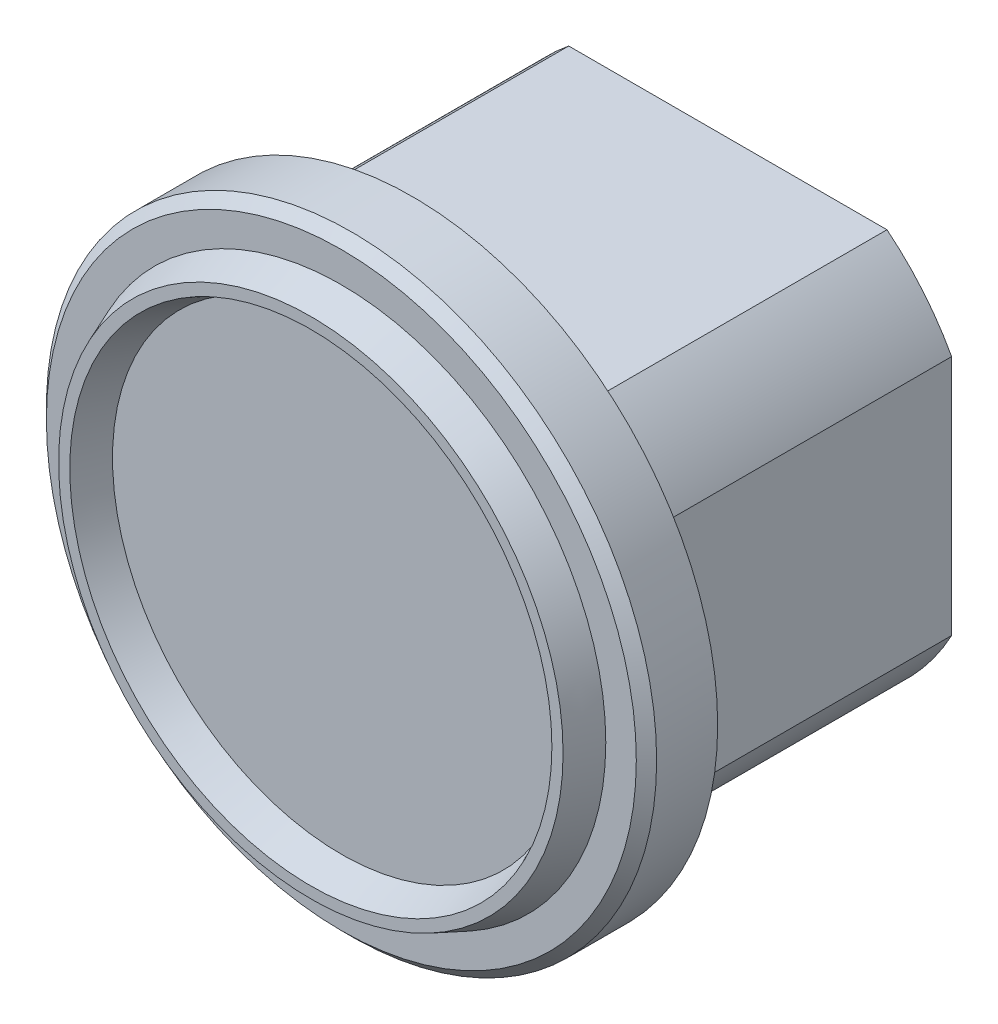
SolidWorks part; units mm, degrees
ref_plane "Ebene vorne" through (0, 0, 0) normal (0, 0, 1) x (1, 0, 0)
ref_plane "Ebene oben" through (0, 0, 0) normal (0, 1, 0) x (1, 0, 0)
ref_plane "Ebene rechts" through (0, 0, 0) normal (1, 0, 0) x (0, 0, -1)
sketch "Skizze1" plane through (0, 0, 0) normal (0, 0, 1) x (1, 0, 0)
  line L0 (22, 39) -> (22, -5.4538) construction
  line L1 (6.3555, 0) -> (37.6445, 0)
  line L2 (0, 7.6257) -> (0, 31.3743)
  line L3 (6.3555, 39) -> (37.6445, 39)
  line L4 (44, 7.6257) -> (44, 31.3743)
  line L5 (22, -5.4538) -> (0, 19.5) construction
  line L6 (0, 19.5) -> (47.6431, 19.5) construction
  arc A0 (0, 7.6257) -> (6.3555, 0) centre (22, 19.5) ccw
  arc A1 (6.3555, 39) -> (0, 31.3743) centre (22, 19.5) ccw
  arc A2 (44, 31.3743) -> (37.6445, 39) centre (22, 19.5) ccw
  arc A3 (37.6445, 0) -> (44, 7.6257) centre (22, 19.5) ccw
  dimension "D3" = 50
  dimension "D1" = 39
extrude "Aufsatz-Linear austragen1" add sketch "Skizze1" along normal blind 31
sketch "Skizze2" plane through (0, 0, 31) normal (0, 0, 1) x (1, 0, 0)
  line L0 (44, 19.5) -> (0.8442, 19.5) construction
  line L1 (44, 7.6257) -> (44, 31.3743) construction
  line L2 (22, 39) -> (22, 7.374) construction
  line L3 (37.6445, 39) -> (6.3555, 39) construction
  circle A0 centre (22, 19.5) radius 30
  dimension "D1" = 60
extrude "Aufsatz-Linear austragen2" add sketch "Skizze2" along normal blind 7
chamfer "Fase1" distance 1 angle 45 1 edges at (52, 19.5, 38)
sketch "Skizze3" plane through (0, 0, 38) normal (0, 0, 1) x (1, 0, 0)
  circle A0 centre (22, 19.5) radius 22.5
  circle A1 centre (22, 19.5) radius 26
  dimension "D1" = 45
  dimension "D2" = 52
extrude "Aufsatz-Linear austragen3" add sketch "Skizze3" along normal blind 3
chamfer "Fase3" distance 3 distance2 1.2 1 edges at (48, 19.5, 41) first distance on face at (48, 19.5, 41)
chamfer "Fase4" distance 1.2 distance2 3 1 edges at (44.5, 19.5, 41) first distance on face at (46.8, 19.5, 41)
